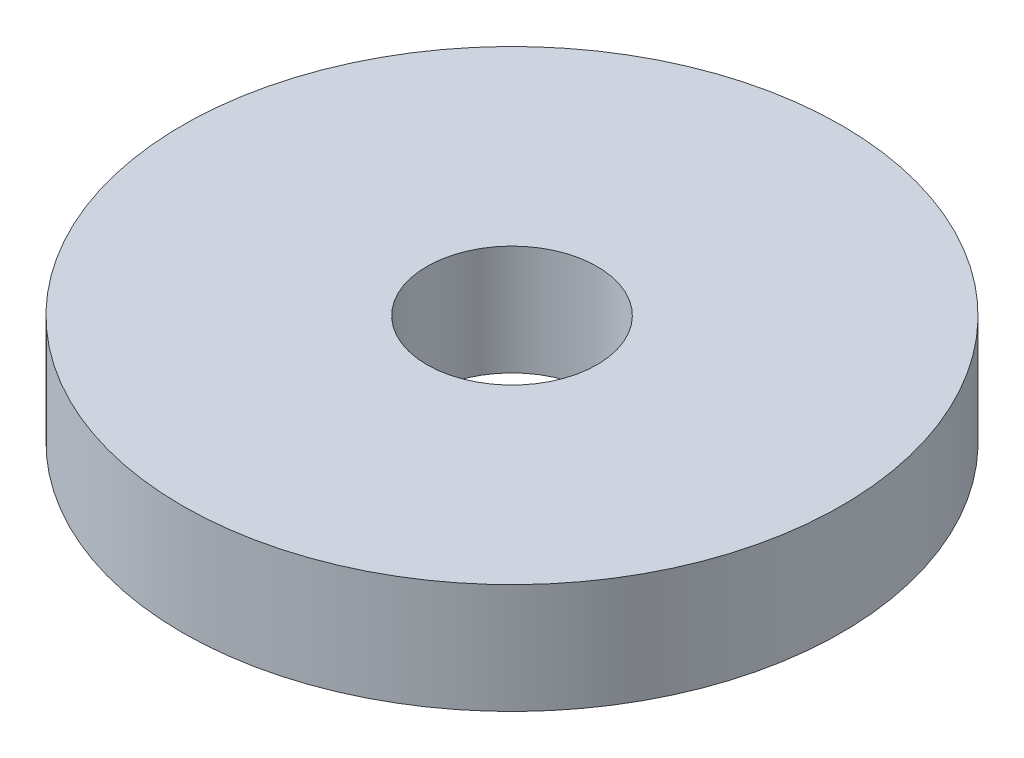
SolidWorks part; units mm, degrees
ref_plane "Plano frontal" through (0, 0, 0) normal (0, 0, 1) x (1, 0, 0)
ref_plane "Plano superior" through (0, 0, 0) normal (0, 1, 0) x (1, 0, 0)
ref_plane "Plano direito" through (0, 0, 0) normal (1, 0, 0) x (0, 0, -1)
sketch "Esboço1" plane through (0, 0, 0) normal (0, 1, 0) x (1, 0, 0)
  circle A0 centre (0, 0) radius 6
  circle A1 centre (0, 0) radius 1.55
  dimension "D1" = 12
  dimension "D2" = 3.1
extrude "Ressalto-extrusão1" add sketch "Esboço1" along normal blind 2
